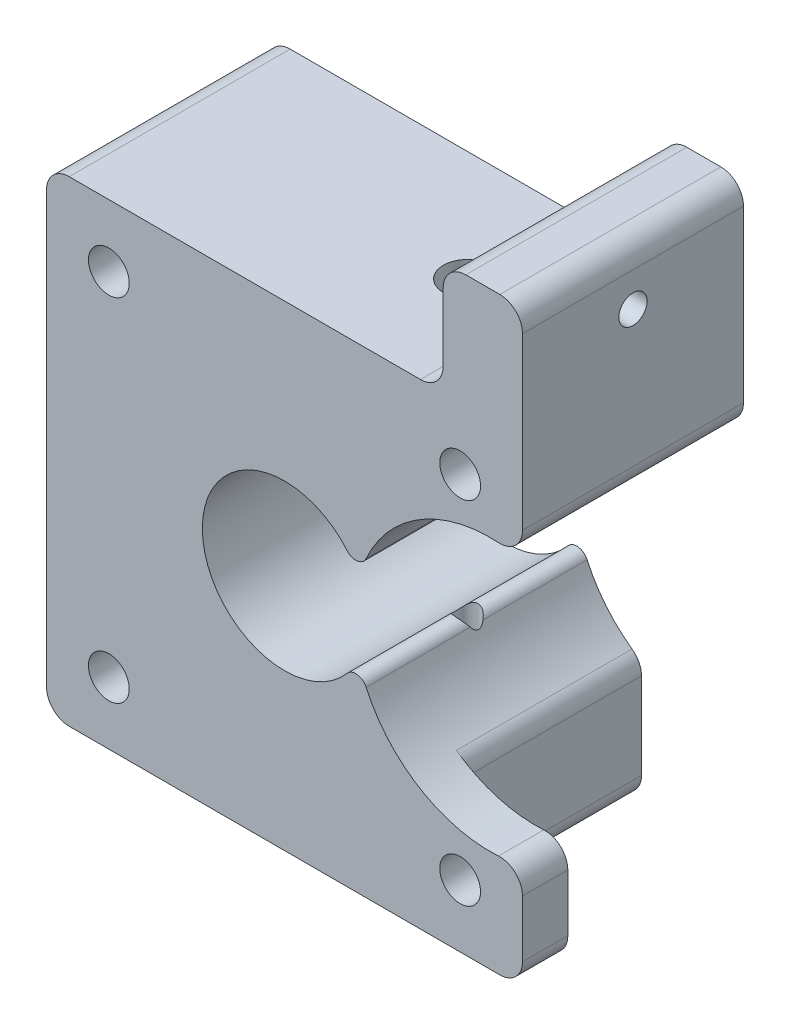
SolidWorks part; units mm, degrees
ref_plane "Front Plane" through (0, 0, 0) normal (0, 0, 1) x (1, 0, 0)
ref_plane "Top Plane" through (0, 0, 0) normal (0, 1, 0) x (1, 0, 0)
ref_plane "Right Plane" through (0, 0, 0) normal (1, 0, 0) x (0, 0, -1)
sketch "Sketch1" plane through (0, 0, 0) normal (0, 0, 1) x (1, 0, 0)
  line L1 (21, 21) -> (-21, 21)
  line L2 (21, 21) -> (21, -21)
  line L3 (21, -21) -> (-21, -21)
  line L4 (-21, 21) -> (-21, -21)
  line L5 (0, -21) -> (0, 21) construction
  line L6 (21, 0) -> (-21, 0) construction
  line L7 (21, 21) -> (14, 21)
  line L8 (21, 21) -> (21, 31)
  line L9 (21, 31) -> (14, 31)
  line L10 (14, 21) -> (14, 31)
  point P0 (0, 0)
  dimension "D1" = 42
  dimension "D2" = 10
  dimension "D3" = 7
extrude "Boss-Extrude1" add sketch "Sketch1" along normal blind 19.5 contours L10 L1 L8 L9 | L3 L4 L1 L2 region at (17.5, 26, 0)
sketch "Sketch2" plane through (0, 0, 19.5) normal (0, 0, 1) x (1, 0, 0)
  circle A0 centre (0, 0) radius 7.25
  dimension "D1" = 14.5
extrude "Cut-Extrude1" cut sketch "Sketch2" against normal blind 22
hole_wizard "M3 Clearance Hole1" positions "Sketch4" profile "Sketch5" hole size "M3" standard "ANSI Metric" end condition through all
sketch "Sketch4" plane through (0, 0, 19.5) normal (0, 0, 1) x (1, 0, 0)
  point P0 (-15.5, 15.5)
  point P2 (15.5, 15.5)
  point P4 (15.5, -15.5)
  point P6 (-15.5, -15.5)
  point P10 (0, 0)
  point P11 (0, 0)
  point P12 (0, 0)
  point P13 (0, 0)
  dimension "D1" = 31
  dimension "D2" = 31
  dimension "D3" = 15.5
  dimension "D4" = 15.5
sketch "Sketch5" plane through (-15.5, 15.5, 19.5) normal (1, 0, 0) x (0, -1, 0)
  line L0 (0, 0) -> (0, 19.5)
  line L1 (0, 19.5) -> (1.8, 19.5)
  line L2 (1.8, 19.5) -> (1.8, 0)
  line L5 (1.8, 0) -> (0, 0)
  line L11 (0, -6.35) -> (0, 107.95) construction
  dimension "Thru Hole Dia." = 3.6
  dimension "Thru Hole Depth" = 19.5
sketch "Sketch6" plane through (0, 0, 19.5) normal (0, 0, 1) x (1, 0, 0)
  circle A0 centre (18.1475, 0) radius 12
  point P2 (0, 0)
  dimension "D1" = 18.1475
  dimension "D2" = 24
extrude "Cut-Extrude2" cut sketch "Sketch6" against normal blind 22
sketch "Sketch7" plane through (0, 0, 0) normal (0, 0, 1) x (1, 0, 0)
  line L0 (21, -11.656) -> (21, -21)
  line L1 (21, -21) -> (12, -21)
  line L2 (21, -21) -> (-21, -21) construction
  line L3 (12, -21) -> (12, -10.3057)
  arc A0 (6.5545, -3.0986) -> (21, -11.656) centre (18.1475, 0) ccw construction
  arc A1 (12, -10.3057) -> (21, -11.656) centre (18.1475, 0) ccw
  dimension "D1" = 9
extrude "Cut-Extrude3" cut sketch "Sketch7" along normal blind 15.5
hole_wizard "M3x0.5 Tapped Hole1" positions "Sketch8" profile "Sketch9" tap size "M3x0.5" standard "ANSI Metric" end condition through all
sketch "Sketch8" plane through (14, 0, 0) normal (-1, 0, 0) x (0, 0, 1)
  line L0 (0, 26) -> (9.75, 26) construction
  line L1 (0, 21) -> (0, 31) construction
  line L2 (9.75, 26) -> (9.75, 31) construction
  line L3 (19.5, 31) -> (0, 31) construction
  point P0 (9.75, 26)
sketch "Sketch9" plane through (14, 26, 9.75) normal (0, 1, 0) x (0, 0, 1)
  line L0 (0, 0) -> (0, 7)
  line L1 (0, 7) -> (1.25, 7)
  line L2 (1.25, 7) -> (1.25, 0)
  line L5 (1.25, 0) -> (0, 0)
  line L11 (0, -6.35) -> (0, 107.95) construction
  dimension "Thru Tap Drill Dia." = 2.5
  dimension "Thru Tap Drill Depth" = 7
cosmetic thread "Hole Thread1" parameters "D2"=3
fillet "Fillet1" radius 1 2 edges at (6.5545, 3.0986, 9.75) (6.5545, -3.0986, 9.75)
hole_wizard "M5x0.8 Tapped Hole1" positions "Sketch10" profile "Sketch11" tap size "M5x0.8" standard "ANSI Metric"
sketch "Sketch10" plane through (0, 21, 0) normal (0, 1, 0) x (1, 0, 0)
  line L0 (-21, -9.75) -> (6.375, -9.75) construction
  line L3 (-21, -19.5) -> (-21, 0) construction
  point P0 (6.375, -9.75)
  point P9 (6.3783, -11)
  point P11 (-21, -11)
  dimension "D1" = 6.375
sketch "Sketch11" plane through (6.375, 21, 9.75) normal (1, 0, 0) x (0, 0, 1)
  line L0 (0, 0) -> (0, 22.2618)
  line L1 (0, 22.2618) -> (2.1, 21)
  line L2 (2.1, 21) -> (2.1, 0)
  line L5 (2.1, 0) -> (0, 0)
  line L10 (0, 22.2618) -> (-2.1, 21) construction
  line L11 (0, -6.35) -> (0, 107.95) construction
  dimension "Tap Drill Dia." = 4.2
  dimension "Tap Drill Depth" = 21
  dimension "Drill Angle" = 118
cosmetic thread "Hole Thread2" parameters "D1"=10, "D2"=5
sketch "Sketch12" plane through (0, 21, 0) normal (0, 1, 0) x (1, 0, 0)
  circle A0 centre (6.375, -9.75) radius 1
  dimension "D1" = 2
extrude "Cut-Extrude4" cut sketch "Sketch12" against normal through all
chamfer "Chamfer1" distance 2 angle 60 1 edges at (6.375, -21, 10.75) first distance on face at (6.375, -21, 10.75)
fillet "Fillet3" radius 2 10 edges at (12, -21, 7.75) (12, -10.3057, 7.75) (21, -11.656, 17.5) (21, -21, 17.5) (-21, -21, 9.75) (-21, 21, 9.75) (14, 21, 9.75) (14, 31, 9.75) (21, 31, 9.75) (21, 11.656, 9.75)
